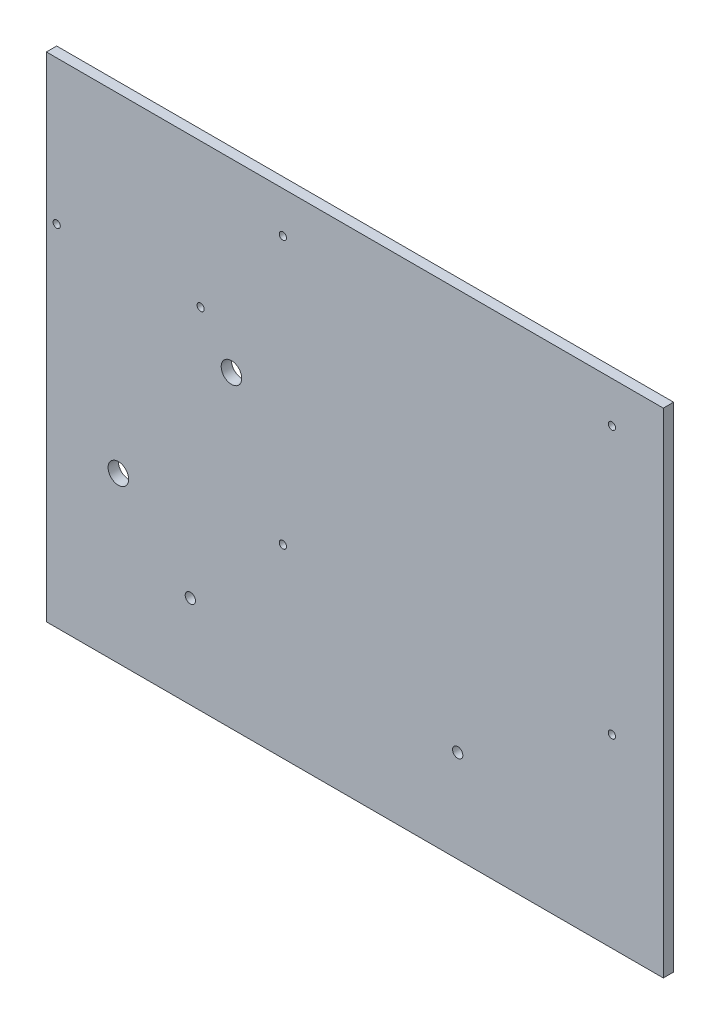
SolidWorks part; units mm, degrees
material "Acrylic (Medium-high impact)"
ref_plane "Front Plane" through (0, 0, 0) normal (0, 0, 1) x (1, 0, 0)
ref_plane "Top Plane" through (0, 0, 0) normal (0, 1, 0) x (1, 0, 0)
ref_plane "Right Plane" through (0, 0, 0) normal (1, 0, 0) x (0, 0, -1)
sketch "Sketch1" plane through (0, 0, 0) normal (0, 0, 1) x (1, 0, 0)
  line L1 (0, 0) -> (381, 0)
  line L2 (0, 0) -> (0, 304.8)
  line L3 (0, 304.8) -> (381, 304.8)
  line L4 (381, 0) -> (381, 304.8)
  dimension "D1" = 381
  dimension "D2" = 304.8
extrude "Boss-Extrude1" add sketch "Sketch1" along normal blind 6.35
sketch "Sketch2" plane through (0, 0, 6.35) normal (0, 0, 1) x (1, 0, 0)
  line L0 (381, 304.8) -> (0, 304.8) construction
  line L1 (0, 304.8) -> (0, 0) construction
  circle A0 centre (6.35, 215.9) radius 2.2225
  circle A1 centre (95.25, 215.9) radius 2.2225
  dimension "D1" = 4.445
  dimension "D2" = 88.9
  dimension "D3" = 88.9
  dimension "D4" = 6.35
extrude "Cut-Extrude1" cut sketch "Sketch2" against normal through all
sketch "Sketch3" plane through (0, 0, 6.35) normal (0, 0, 1) x (1, 0, 0)
  line L1 (0, 0) -> (381, 0) construction
  line L2 (0, 304.8) -> (0, 0) construction
  circle A0 centre (88.9, 57.15) radius 3.175
  circle A1 centre (254, 57.15) radius 3.175
  point P9 (190.5, 0)
  dimension "D2" = 6.35
  dimension "D1" = 165.1
  dimension "D3" = 88.9
  dimension "D4" = 57.15
extrude "Cut-Extrude2" cut sketch "Sketch3" against normal through all
hole_wizard "#8 Clearance Hole1" positions "Sketch4" profile "Sketch5" hole size "#8" standard "ANSI Inch" end condition through all
sketch "Sketch4" plane through (0, 0, 6.35) normal (0, 0, 1) x (1, 0, 0)
  line L1 (381, 0) -> (381, 304.8) construction
  circle A1 centre (254, 57.15) radius 3.175 construction
  point P0 (146.05, 114.3)
  point P2 (349.25, 114.3)
  point P15 (146.05, 279.4)
  point P17 (349.25, 279.4)
  dimension "D1" = 203.2
  dimension "D2" = 31.75
  dimension "D3" = 57.15
  dimension "D4" = 165.1
sketch "Sketch5" plane through (146.05, 114.3, 6.35) normal (1, 0, 0) x (0, -1, 0)
  line L0 (0, 0) -> (0, 6.35)
  line L1 (0, 6.35) -> (2.2479, 6.35)
  line L2 (2.2479, 6.35) -> (2.2479, 0)
  line L5 (2.2479, 0) -> (0, 0)
  line L11 (0, -6.35) -> (0, 107.95) construction
  dimension "Thru Hole Dia." = 4.4958
  dimension "Thru Hole Depth" = 6.35
sketch "Sketch6" plane through (0, 0, 6.35) normal (0, 0, 1) x (1, 0, 0)
  line L1 (0, 0) -> (381, 0) construction
  circle A0 centre (114.3, 190.5) radius 6.35
  circle A2 centre (95.25, 215.9) radius 2.2225 construction
  dimension "D1" = 184.15
  dimension "D2" = 12.7
  dimension "D3" = 12.7
extrude "Cut-Extrude3" cut sketch "Sketch6" against normal through all
sketch "Sketch7" plane through (0, 0, 6.35) normal (0, 0, 1) x (1, 0, 0)
  line L0 (0, 304.8) -> (0, 0) construction
  circle A0 centre (44.45, 101.6) radius 6.35
  circle A1 centre (88.9, 57.15) radius 3.175 construction
  dimension "D1" = 12.7
  dimension "D2" = 38.1
  dimension "D3" = 44.45
extrude "Cut-Extrude4" cut sketch "Sketch7" against normal through all
